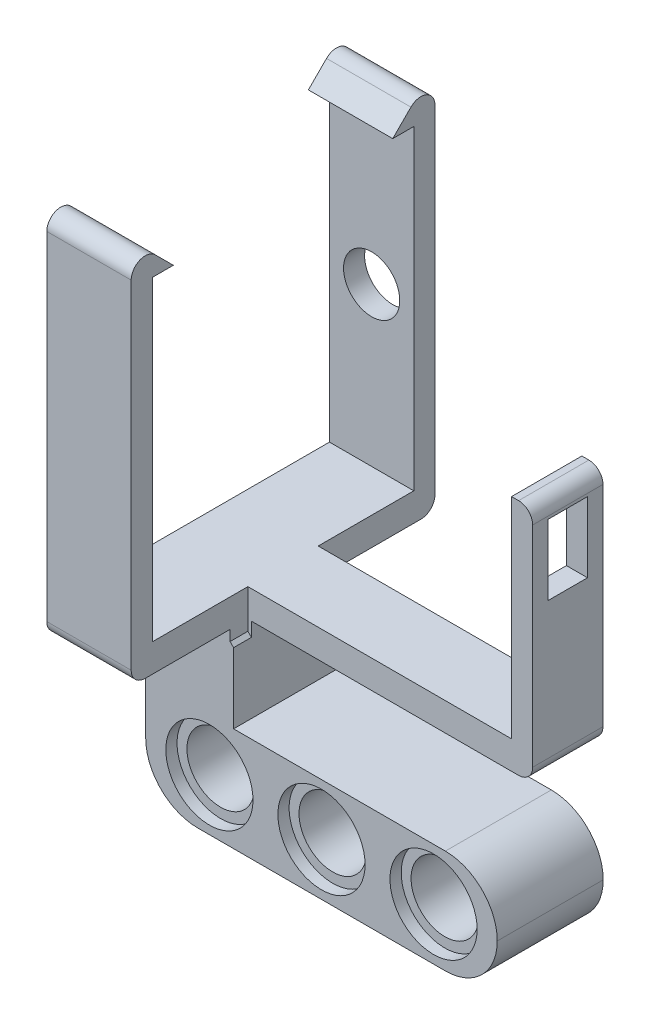
SolidWorks part; units mm, degrees
ref_plane "Front Plane" through (0, 0, 0) normal (0, 0, 1) x (1, 0, 0)
ref_plane "Top Plane" through (0, 0, 0) normal (0, 1, 0) x (1, 0, 0)
ref_plane "Right Plane" through (0, 0, 0) normal (1, 0, 0) x (0, 0, -1)
sketch "Sketch1" plane through (0, 0, 0) normal (0, 1, 0) x (1, 0, 0)
  line L1 (-18.5, -10.8) -> (18.5, -10.8)
  line L2 (-18.5, -10.8) -> (-18.5, 10.8)
  line L3 (-18.5, 10.8) -> (18.5, 10.8)
  line L4 (18.5, -10.8) -> (18.5, 10.8)
  dimension "D1" = 21.6
  dimension "D2" = 37
  dimension "D3" = 18.5
  dimension "D4" = 10.8
extrude "Boss-Extrude1" add sketch "Sketch1" along normal blind 2
sketch "Sketch2" plane through (0, 2, 0) normal (0, 1, 0) x (1, 0, 0)
  line L0 (18.5, -10.8) -> (18.5, 10.8) construction
  line L1 (-7.75, 10.8) -> (-1.75, 10.8)
  line L2 (-7.75, 10.8) -> (-7.75, 9.3)
  line L3 (-7.75, 9.3) -> (-1.75, 9.3)
  line L4 (-1.75, 10.8) -> (-1.75, 9.3)
  line L5 (18.5, 10.8) -> (-18.5, 10.8) construction
  line L6 (20.9449, 0) -> (-19.9732, 0) construction
  line L7 (-18.5, 10.8) -> (-18.5, -10.8) construction
  line L8 (-7.75, -9.3) -> (-1.75, -9.3)
  line L9 (-1.75, -10.8) -> (-1.75, -9.3)
  line L10 (-7.75, -10.8) -> (-1.75, -10.8)
  line L11 (-7.75, -10.8) -> (-7.75, -9.3)
  line L13 (18.5, 2.5) -> (17, 2.5)
  line L14 (18.5, 2.5) -> (18.5, -2.5)
  line L15 (18.5, -2.5) -> (17, -2.5)
  line L16 (17, 2.5) -> (17, -2.5)
  line L17 (-18.5, -10.8) -> (18.5, -10.8) construction
  dimension "D1" = 20.25
  dimension "D2" = 0
  dimension "D3" = 0
  dimension "D4" = 90
  dimension "D5" = 6
  dimension "D6" = 1.5
  dimension "D7" = 0
  dimension "D8" = 5
  dimension "D9" = 8.3
  dimension "D10" = 1.5
extrude "Boss-Extrude2" add sketch "Sketch2" along normal blind 22.44
sketch "Sketch3" plane through (0, 24.44, 0) normal (0, 1, 0) x (1, 0, 0)
  line L0 (-7.75, 10.8) -> (-7.75, 9.3) construction
  line L1 (-7.75, 10.8) -> (-1.75, 10.8)
  line L2 (-7.75, 10.8) -> (-7.75, 7.8)
  line L3 (-7.75, 7.8) -> (-1.75, 7.8)
  line L4 (-1.75, 10.8) -> (-1.75, 7.8)
  line L5 (-1.75, 9.3) -> (-1.75, 10.8) construction
  line L6 (-1.75, 10.8) -> (-7.75, 10.8) construction
  dimension "D1" = 0
  dimension "D2" = 0
  dimension "D3" = 0
  dimension "D4" = 3
extrude "Boss-Extrude3" add sketch "Sketch3" along normal blind 5
chamfer "Chamfer1" distance 5 distance2 5 1 edges at (-4.75, 29.44, -7.8)
sketch "Sketch4" plane through (0, 24.44, 0) normal (0, 1, 0) x (1, 0, 0)
  line L0 (-1.75, -10.8) -> (-1.75, -9.3) construction
  line L1 (-7.75, -10.8) -> (-1.75, -10.8)
  line L2 (-7.75, -10.8) -> (-7.75, -7.8)
  line L3 (-7.75, -7.8) -> (-1.75, -7.8)
  line L4 (-1.75, -10.8) -> (-1.75, -7.8)
  line L5 (-7.75, -10.8) -> (-1.75, -10.8) construction
  line L6 (-7.75, -9.3) -> (-7.75, -10.8) construction
  dimension "D1" = 0
  dimension "D2" = 0
  dimension "D3" = 0
  dimension "D4" = 3
extrude "Boss-Extrude4" add sketch "Sketch4" along normal blind 5
chamfer "Chamfer2" distance 5 distance2 5 1 edges at (-4.75, 29.44, 7.8)
sketch "Sketch6" plane through (18.5, 0, 0) normal (1, 0, 0) x (0, 0, -1)
  line L0 (-2.5, 24.44) -> (2.5, 24.44) construction
  line L1 (-2.5, 24.44) -> (2.5, 24.44)
  line L2 (-2.5, 24.44) -> (-2.5, 16.92)
  line L3 (-2.5, 16.92) -> (2.5, 16.92)
  line L4 (2.5, 24.44) -> (2.5, 16.92)
  line L5 (2.5, 24.44) -> (2.5, 2) construction
  line L6 (-2.5, 24.44) -> (-2.5, 2) construction
  line L8 (-1.4, 15.72) -> (1.4, 15.72)
  line L9 (-1.4, 15.72) -> (-1.4, 10.72)
  line L10 (-1.4, 10.72) -> (1.4, 10.72)
  line L11 (1.4, 15.72) -> (1.4, 10.72)
  point P4 (0, 24.44)
  dimension "D1" = 0
  dimension "D2" = 0
  dimension "D3" = 0
  dimension "D4" = 7.52
  dimension "D5" = 1.2
  dimension "D6" = 1.1
  dimension "D7" = 5
  dimension "D8" = 1.1
extrude "Cut-Extrude1" cut sketch "Sketch6" against normal blind 5
sketch "Sketch7" plane through (0, 2, 0) normal (0, 1, 0) x (1, 0, 0)
  line L1 (-1.6117, 10.6418) -> (18.4299, 10.6418)
  line L2 (-1.6117, 10.6418) -> (-1.6117, 2.6648)
  line L3 (-1.6117, 2.6648) -> (18.4299, 2.6648)
  line L4 (18.4299, 10.6418) -> (18.4299, 2.6648)
sketch "Sketch8" plane through (0, 2, 0) normal (0, 1, 0) x (1, 0, 0)
  line L0 (-1.75, 10.8) -> (-1.75, 7.8) construction
  line L1 (18.5, 10.8) -> (-1.75, 10.8)
  line L2 (18.5, 10.8) -> (18.5, 2.5)
  line L3 (18.5, 2.5) -> (-1.75, 2.5)
  line L4 (-1.75, 10.8) -> (-1.75, 2.5)
  line L5 (18.5, 10.8) -> (-1.75, 10.8) construction
  line L7 (17, 2.5) -> (18.5, 2.5) construction
  line L10 (18.5, -10.8) -> (18.5, -2.5) construction
  line L11 (-1.75, -2.5) -> (18.5, -2.5)
  line L12 (-1.75, -2.5) -> (-1.75, -10.8)
  line L13 (-1.75, -10.8) -> (18.5, -10.8)
  line L14 (18.5, -2.5) -> (18.5, -10.8)
  line L15 (17, -2.5) -> (18.5, -2.5) construction
  line L16 (-1.75, -10.8) -> (18.5, -10.8) construction
  line L17 (-1.75, -7.8) -> (-1.75, -10.8) construction
  line L18 (-18.5, 10.8) -> (-18.5, -10.8) construction
  line L19 (-18.5, 10.8) -> (-7.75, 10.8)
  line L20 (-18.5, 10.8) -> (-18.5, -10.8)
  line L21 (-18.5, -10.8) -> (-7.75, -10.8)
  line L22 (-7.75, 10.8) -> (-7.75, -10.8)
  line L23 (-18.5, -10.8) -> (-7.75, -10.8) construction
  line L24 (-7.75, 10.8) -> (-18.5, 10.8) construction
  line L26 (18.5, 2.5) -> (18.5, 10.8) construction
  dimension "D1" = 0
  dimension "D2" = 0
  dimension "D3" = 0
  dimension "D4" = 0
  dimension "D5" = 0
  dimension "D6" = 0
  dimension "D7" = 0
  dimension "D8" = 0
  dimension "D9" = 0
  dimension "D10" = 0
  dimension "D11" = 0
  dimension "D12" = 0
extrude "Cut-Extrude3" cut sketch "Sketch8" against normal blind 10
fillet "Fillet1" radius 1 5 edges at (-4.75, 27.44, -10.8) (-4.75, 27.44, 10.8) (-4.75, 0, 10.8) (-4.75, 0, -10.8) (18.5, 0, 0)
fillet "Fillet2" radius 1 1 edges at (18.5, 16.92, 0)
sketch "Sketch9" plane through (0, 0, -9.3) normal (0, 0, 1) x (1, 0, 0)
  line L0 (-7.75, 2) -> (-1.75, 2) construction
  line L1 (-7.75, 24.44) -> (-7.75, 2) construction
  circle A0 centre (-4.75, 13.22) radius 2
  point P6 (-4.5283, 16.4828)
  dimension "D3" = 4
  dimension "D1" = 11.22
  dimension "D2" = 3
extrude "Cut-Extrude4" cut sketch "Sketch9" against normal blind 10
sketch "Sketch10" plane through (0, 0, 0) normal (0, -1, 0) x (1, 0, 0)
  line L1 (17.25, 3.88) -> (-7.75, 3.88)
  line L2 (17.25, 3.88) -> (17.25, -3.88)
  line L3 (17.25, -3.88) -> (-7.75, -3.88)
  line L4 (-7.75, 3.88) -> (-7.75, -3.88)
  line L5 (-7.75, -9.8) -> (-7.75, 9.8) construction
  dimension "D1" = 7.76
  dimension "D2" = 3.88
  dimension "D3" = 25
  dimension "D4" = 0
sketch "Sketch13" plane through (0, 0, 0) normal (0, -1, 0) x (1, 0, 0)
  line L0 (-7.75, -9.8) -> (-7.75, 9.8) construction
  line L1 (-7.75, 3.767) -> (17.25, 3.767)
  line L2 (-7.75, 3.767) -> (-7.75, -3.767)
  line L3 (-7.75, -3.767) -> (17.25, -3.767)
  line L4 (17.25, 3.767) -> (17.25, -3.767)
  point P7 (0.5055, 2.6972)
  dimension "D1" = 25
  dimension "D2" = 3.767
  dimension "D3" = 3.767
  dimension "D4" = 0
extrude "Boss-Extrude5" add sketch "Sketch13" along normal blind 13.38
sketch "Sketch14" plane through (0, 0, 3.767) normal (0, 0, 1) x (1, 0, 0)
  line L0 (17.25, -13.38) -> (-7.75, -13.38) construction
  line L1 (-7.75, -13.38) -> (-7.75, 0) construction
  circle A0 centre (4.75, -9.69) radius 2.4
  circle A1 centre (12.72, -9.69) radius 2.4
  circle A2 centre (-3.22, -9.69) radius 2.4
  point P10 (0, 0)
  point P12 (4.6671, -9.6693)
  dimension "D3" = 4.8
  dimension "D5" = 4.8
  dimension "D7" = 4.8
  dimension "D1" = 3.69
  dimension "D2" = 12.5
  dimension "D4" = 7.97
  dimension "D6" = 3.69
  dimension "D8" = 7.97
extrude "Cut-Extrude5" cut sketch "Sketch14" against normal blind 7.92
sketch "Sketch15" plane through (0, 0, 3.767) normal (0, 0, 1) x (1, 0, 0)
  line L1 (17.25, -13.38) -> (-7.75, -13.38) construction
  line L2 (17.25, -13.38) -> (17.25, 0) construction
  line L3 (1.0302, -12.0913) -> (1.0137, -12.0913)
  line L4 (1.0302, -12.0913) -> (1.0302, -12.1691)
  line L5 (1.0302, -12.1691) -> (1.0137, -12.1691)
  line L6 (1.0137, -12.0913) -> (1.0137, -12.1691)
  circle A0 centre (-3.22, -9.69) radius 3.1
  circle A1 centre (4.75, -9.69) radius 3.1
  circle A2 centre (12.72, -9.69) radius 3.1
  dimension "D1" = 3.69
  dimension "D6" = 6.2
  dimension "D7" = 6.2
  dimension "D8" = 6.2
  dimension "D2" = 7.97
  dimension "D3" = 3.69
  dimension "D4" = 7.97
  dimension "D5" = 3.69
  dimension "D9" = 12.5
extrude "Cut-Extrude6" cut sketch "Sketch15" against normal blind 0.8
sketch "Sketch16" plane through (0, 0, -3.767) normal (0, 0, -1) x (-1, 0, 0)
  line L0 (7.75, -13.38) -> (7.75, 0) construction
  line L1 (7.75, -13.38) -> (-17.25, -13.38) construction
  circle A0 centre (-4.75, -9.69) radius 3.1
  circle A1 centre (3.22, -9.69) radius 3.1
  circle A2 centre (-12.72, -9.69) radius 3.1
  dimension "D3" = 6.2
  dimension "D8" = 6.2
  dimension "D9" = 6.2
  dimension "D1" = 12.5
  dimension "D2" = 3.69
  dimension "D4" = 7.97
  dimension "D5" = 7.97
  dimension "D6" = 3.69
  dimension "D7" = 3.69
extrude "Cut-Extrude7" cut sketch "Sketch16" against normal blind 0.8
sketch "Sketch19" plane through (0, 0, -3.767) normal (0, 0, -1) x (-1, 0, 0)
  line L0 (1.75, 0) -> (-17.25, 0) construction
  line L1 (-17.25, 0) -> (1.5, 0)
  line L2 (-17.25, 0) -> (-17.25, -6)
  line L3 (-17.25, -6) -> (1.5, -6)
  line L4 (1.5, 0) -> (1.5, -6)
  line L5 (-17.25, -13.38) -> (-17.25, 0) construction
  line L7 (7.75, -13.38) -> (-17.25, -13.38) construction
  dimension "D1" = 0
  dimension "D2" = 0
  dimension "D3" = 18.75
  dimension "D4" = 7.38
extrude "Cut-Extrude8" cut sketch "Sketch19" against normal blind 10
fillet "Fillet3" radius 3.69 3 edges at (-7.75, -13.38, 0) (17.25, -13.38, 0) (17.25, -6, 0)
chamfer "Chamfer3" distance 1 distance2 1 1 edges at (-1.5, 0, -3.1335)
chamfer "Chamfer4" distance 1 angle 45 1 edges at (-1.5, 0, 3.1335)
